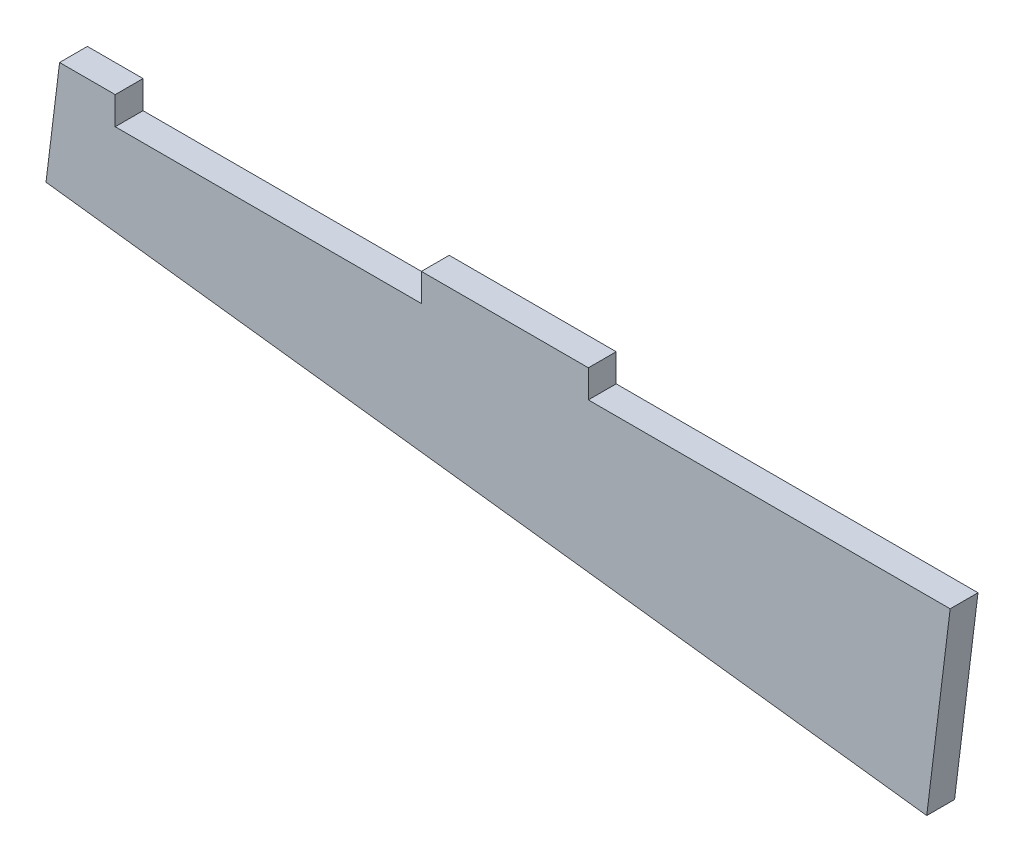
SolidWorks part; units mm, degrees
ref_plane "Front Plane" through (0, 0, 0) normal (0, 0, 1) x (1, 0, 0)
ref_plane "Top Plane" through (0, 0, 0) normal (0, 1, 0) x (1, 0, 0)
ref_plane "Right Plane" through (0, 0, 0) normal (1, 0, 0) x (0, 0, -1)
sketch "Sketch1" plane through (0, 0, 0) normal (0, 0, 1) x (1, 0, 0)
  line L0 (-195.3168, -62.6592) -> (-182.6168, -62.6592)
  line L4 (-182.6168, -62.6592) -> (-182.6168, -69.0092)
  line L5 (-182.6168, -69.0092) -> (-112.7668, -69.0092)
  line L6 (-112.7668, -69.0092) -> (-112.7668, -62.6592)
  line L7 (-112.7668, -62.6592) -> (-74.6668, -62.6592)
  line L8 (-74.6668, -62.6592) -> (-74.6668, -69.0092)
  line L9 (-74.6668, -69.0092) -> (7.8832, -69.0092)
  line L10 (7.8832, -69.0092) -> (2.5379, -112.5435)
  line L11 (2.5379, -112.5435) -> (-198.4122, -87.8699)
  line L12 (-198.4122, -87.8699) -> (-195.3168, -62.6592)
  line L13 (-360.4168, -20.6725) -> (-341.5088, -22.9941) construction
  dimension "D1" = 12.7
  dimension "D2" = 6.35
  dimension "D3" = 69.85
  dimension "D4" = 38.1
  dimension "D5" = 82.55
  dimension "D6" = 25.4
extrude "Boss-Extrude1" add sketch "Sketch1" against normal blind 6.35
